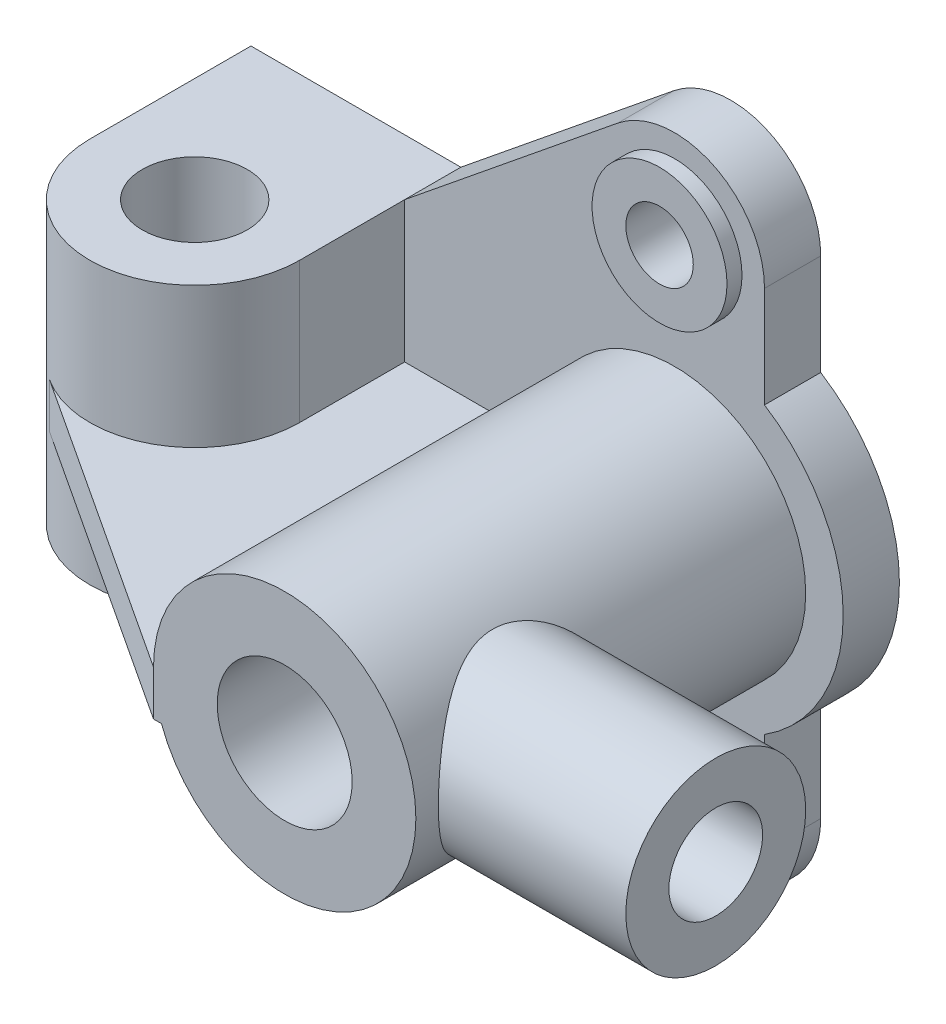
SolidWorks part; units mm, degrees
ref_plane "Front Plane" through (0, 0, 0) normal (0, 0, 1) x (1, 0, 0)
ref_plane "Top Plane" through (0, 0, 0) normal (0, 1, 0) x (1, 0, 0)
ref_plane "Right Plane" through (0, 0, 0) normal (1, 0, 0) x (0, 0, -1)
sketch "Sketch1" plane through (0, 0, 0) normal (0, 0, 1) x (1, 0, 0)
  line L0 (0, -37.5) -> (0, 37.5)
  line L1 (0, 37.5) -> (56, 37.5)
  line L2 (56, 37.5) -> (112.8809, 83.639)
  line L3 (152, 65) -> (152, 38.0657)
  line L4 (0, 0) -> (173, 0) construction
  line L5 (56, -37.5) -> (112.8809, -83.639)
  line L6 (0, -37.5) -> (56, -37.5)
  line L7 (152, -38.0657) -> (152, -65)
  arc A0 (112.8809, 83.639) -> (152, 65) centre (128, 65) cw
  arc A1 (112.8809, -83.639) -> (152, -65) centre (128, -65) ccw
  circle A2 centre (128, 65) radius 18
  circle A3 centre (128, 65) radius 9
  arc A4 (152, -38.0657) -> (152, 38.0657) centre (128, 0) ccw
  circle A5 centre (128, 0) radius 35
  circle A6 centre (128, 0) radius 18
  circle A7 centre (128, -65) radius 9
  circle A8 centre (128, -65) radius 18
  point P16 (173, 0)
  dimension "D1" = 75
  dimension "D4" = 36
  dimension "D5" = 18
  dimension "D6" = 36
  dimension "D7" = 70
  dimension "D8" = 24
  dimension "D9" = 45
  dimension "D2" = 128
  dimension "D3" = 56
  dimension "D10" = 130
extrude "Boss-Extrude1" add sketch "Sketch1" along normal blind 15 contours L0 L4 A5 A4 L3 A0 L2 L1 A2 | L4 L0 L6 L5 A1 L7 A4 A5 A8 region at (79.4121, -31.5007, 0) region at (79.4121, 31.5007, 0)
extrude "Boss-Extrude2" add sketch "Sketch1<4>" along normal blind 19 contours A2 A3 | A8 A7 region at (110.5091, 65, 0) region at (110.5091, -65, 0)
sketch "Sketch1<4>" plane through (0, 0, 0) normal (0, 0, 1) x (1, 0, 0) same geometry as "Sketch1"
extrude "Boss-Extrude3" add sketch "Sketch1<5>" along normal blind 119 contours A5 L4 A6 | L4 A5 A6 region at (128, 34.2174, 0) region at (101.5, -0.7826, 0)
sketch "Sketch1<5>" plane through (0, 0, 0) normal (0, 0, 1) x (1, 0, 0) same geometry as "Sketch1"
sketch "Sketch2" plane through (0, 0, 0) normal (0, 1, 0) x (1, 0, 0)
  line L0 (56, -15) -> (56, 0) construction
  line L1 (0, -15) -> (0, 0) construction
  line L2 (0, -15) -> (56, -15) construction
  line L3 (56, -15) -> (56, -43)
  line L4 (0, -43) -> (0, -15)
  line L5 (0, -15) -> (56, -15)
  arc A0 (0, -43) -> (56, -43) centre (28, -43) ccw
  circle A1 centre (28, -43) radius 14
  dimension "D1" = 28
extrude "Boss-Extrude4" add sketch "Sketch2" along normal up to surface and the other way up to surface up to face at (28, 37.5, 7.5) other way up to face at (28, -37.5, 7.5)
sketch "Sketch3" plane through (0, 0, 0) normal (0, 1, 0) x (1, 0, 0)
  line L0 (93, -119) -> (12.6676, -66.429)
  line L1 (56, -15) -> (56, -43) construction
  line L2 (56, -15) -> (56, -43)
  line L3 (56, -15) -> (93, -15)
  line L4 (93, -119) -> (110, -119)
  line L5 (110, -119) -> (146, -119) construction
  line L6 (93, -119) -> (163, -119) construction
  line L7 (110, -119) -> (110, -15)
  line L8 (110, -15) -> (93, -15)
  arc A0 (12.6676, -66.429) -> (56, -43) centre (28, -43) ccw
  arc A1 (0, -43) -> (56, -43) centre (28, -43) ccw construction
extrude "Boss-Extrude5" add sketch "Sketch3" against normal blind 12
sketch "Sketch4" plane through (0, 0, 0) normal (-1, 0, 0) x (0, 0, 1)
  circle A0 centre (89, 0) radius 24
  circle A1 centre (89, 0) radius 12.5
  dimension "D1" = 48
  dimension "D2" = 25
  dimension "D3" = 89
extrude "Boss-Extrude7" add sketch "Sketch4" along normal up to surface (50 mm away) from offset 213 up to face at (128.2631, 0.0465, 67) offset against normal yes
extrude "Cut-Extrude1" cut sketch "Sketch4<3>" along normal up to surface (67 mm away) from offset 213 contours A1 region at (0, 0, 89) up to face at (146, 0, 119) offset against normal yes
sketch "Sketch4<3>" plane through (0, 0, 0) normal (-1, 0, 0) x (0, 0, 1) same geometry as "Sketch4"
